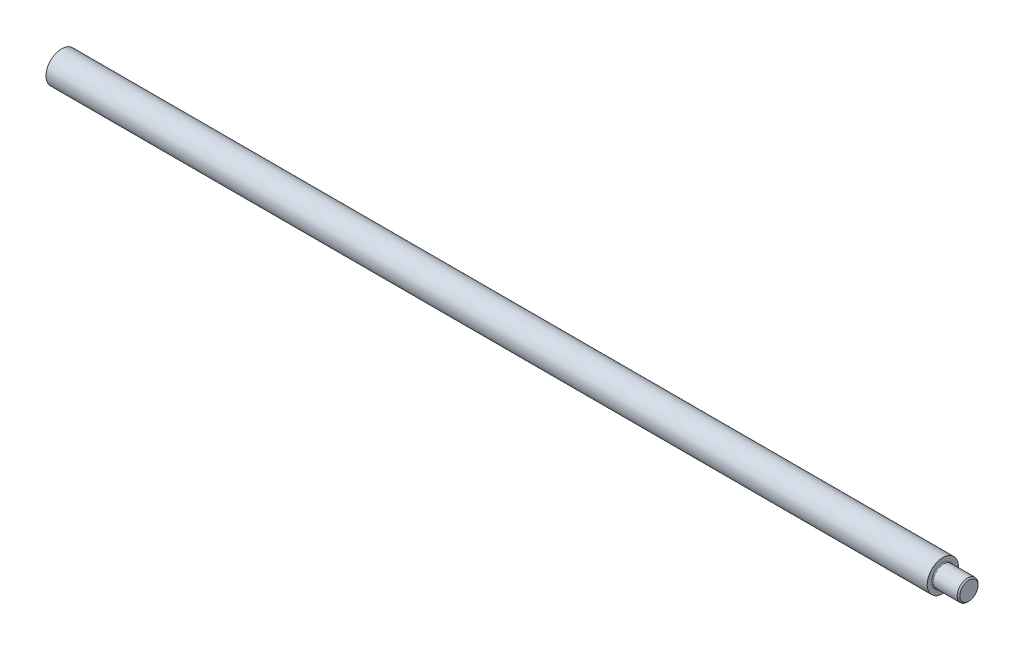
SolidWorks part; units mm, degrees
ref_plane "Piano frontale" through (0, 0, 0) normal (0, 0, 1) x (1, 0, 0)
ref_plane "Piano superiore" through (0, 0, 0) normal (0, 1, 0) x (1, 0, 0)
ref_plane "Piano destro" through (0, 0, 0) normal (1, 0, 0) x (0, 0, -1)
sketch "Sketch1" plane through (0, 0, 0) normal (0, 0, 1) x (1, 0, 0)
  line L0 (30, 5.6842) -> (30, 0)
  line L1 (30, 0) -> (360, 0)
  line L2 (360, 0) -> (360, 3.3158)
  line L3 (360, 3.3158) -> (359.5263, 3.7895)
  line L4 (359.5263, 3.7895) -> (350.8105, 3.7895)
  line L5 (350.5263, 4.0737) -> (350.5263, 5.6842)
  line L6 (350.5263, 5.6842) -> (30, 5.6842)
  line L7 (30, 0) -> (360, 0) construction
  arc A0 (350.8105, 3.7895) -> (350.5263, 4.0737) centre (350.8105, 4.0737) cw
  dimension "D1" = 330
revolve "Revolve1" add sketch "Sketch1" angle 360 about L7 reverse direction yes
